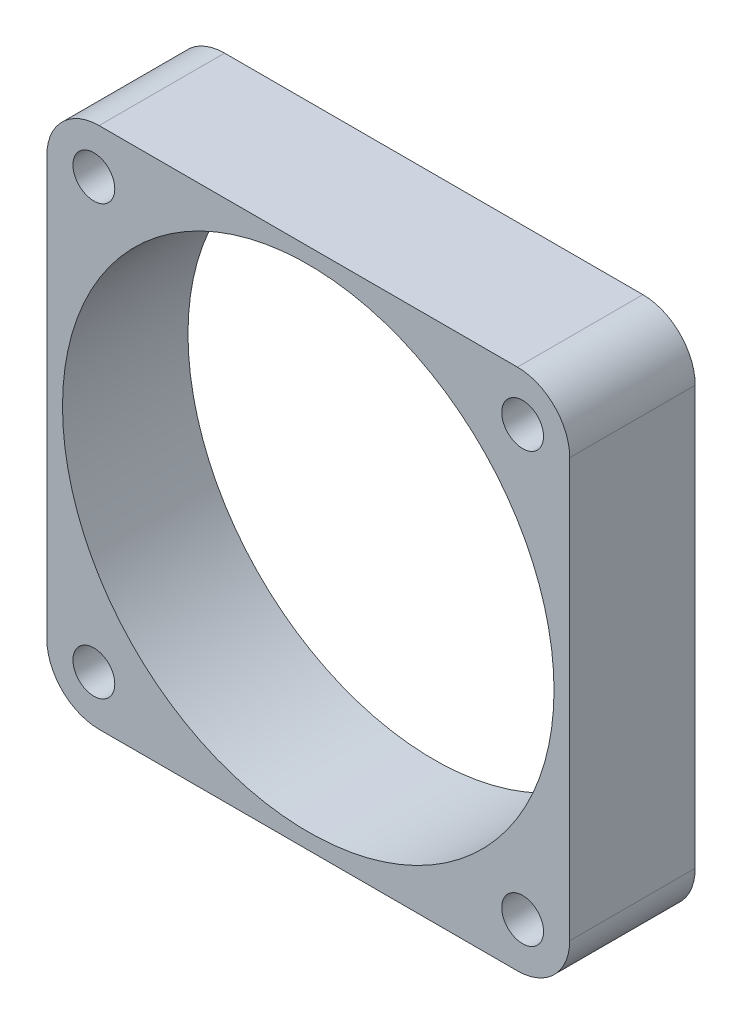
SolidWorks part; units mm, degrees
ref_plane "前视基准面" through (0, 0, 0) normal (0, 0, 1) x (1, 0, 0)
ref_plane "上视基准面" through (0, 0, 0) normal (0, 1, 0) x (1, 0, 0)
ref_plane "右视基准面" through (0, 0, 0) normal (1, 0, 0) x (0, 0, -1)
sketch "草图1" plane through (0, 0, 0) normal (0, 0, 1) x (1, 0, 0)
  line L0 (-1.2062, -43.8665) -> (-51.2062, 6.1335) construction
  line L1 (-51.2062, 6.1335) -> (-1.2062, 6.1335)
  line L2 (-51.2062, 6.1335) -> (-51.2062, -43.8665)
  line L3 (-51.2062, -43.8665) -> (-1.2062, -43.8665)
  line L4 (-1.2062, 6.1335) -> (-1.2062, -43.8665)
  line L5 (-51.2062, -43.8665) -> (-1.2062, 6.1335) construction
  circle A0 centre (-46.7062, -39.3665) radius 2
  circle A1 centre (-5.7062, -39.3665) radius 2
  circle A2 centre (-5.7062, 1.6335) radius 2
  circle A3 centre (-46.7062, 1.6335) radius 2
  circle A4 centre (-26.2062, -18.8665) radius 23.5
  point P12 (0, 0)
  point P13 (-26.2062, -18.8665)
  dimension "D3" = 4
  dimension "D8" = 47
  dimension "D1" = 50
  dimension "D2" = 50
  dimension "D4" = 4.5
  dimension "D5" = 4.5
  dimension "D6" = 4.5
  dimension "4.95" = 4.5
extrude "凸台-拉伸1" add sketch "草图1" along normal blind 12
fillet "圆角1" radius 5 4 edges at (-51.2062, -43.8665, 6) (-51.2062, 6.1335, 6) (-1.2062, -43.8665, 6) (-1.2062, 6.1335, 6)
